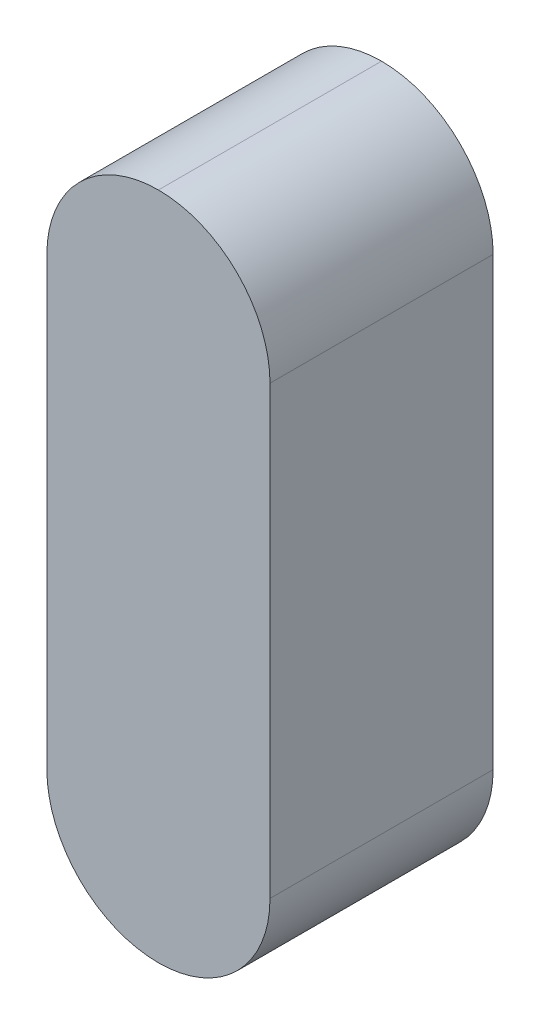
SolidWorks part; units mm, degrees
ref_plane "前视基准面" through (0, 0, 0) normal (0, 0, 1) x (1, 0, 0)
ref_plane "上视基准面" through (0, 0, 0) normal (0, 1, 0) x (1, 0, 0)
ref_plane "右视基准面" through (0, 0, 0) normal (1, 0, 0) x (0, 0, -1)
sketch "Sketch1" plane through (0, 0, 0) normal (0, 1, 0) x (1, 0, 0)
  line L1 (-2, 2) -> (2, 2)
  line L2 (-2, 2) -> (-2, -2)
  line L3 (-2, -2) -> (2, -2)
  line L4 (2, 2) -> (2, -2)
  line L5 (-2, 2) -> (2, -2) construction
  line L6 (-2, -2) -> (2, 2) construction
  point P0 (0, 0)
  dimension "D1" = 4
  dimension "D2" = 4
extrude "Boss-Extrude1" add sketch "Sketch1" along normal mid plane 12
fillet "Fillet1" radius 2 4 edges at (2, -6, 0) (-2, -6, 0) (2, 6, 0) (-2, 6, 0)
